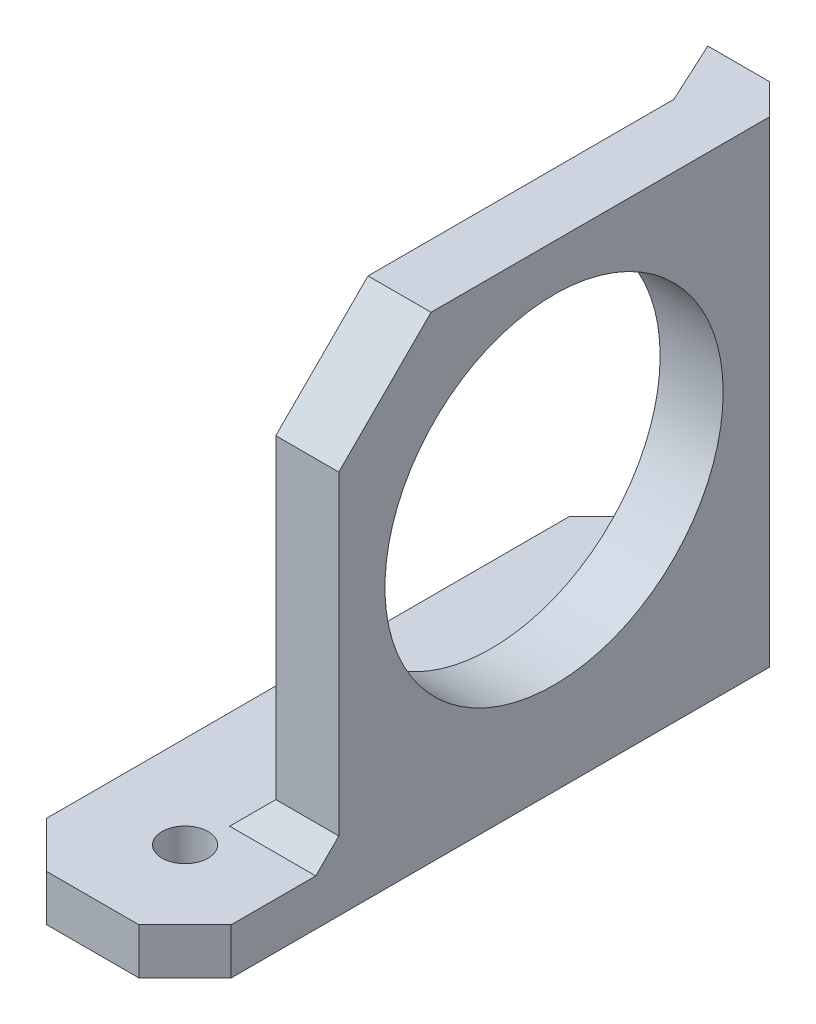
SolidWorks part; units mm, degrees
ref_plane "Front Plane" through (0, 0, 0) normal (0, 0, 1) x (1, 0, 0)
ref_plane "Top Plane" through (0, 0, 0) normal (0, 1, 0) x (1, 0, 0)
ref_plane "Right Plane" through (0, 0, 0) normal (1, 0, 0) x (0, 0, -1)
sketch "Sketch1" plane through (0, 0, 0) normal (0, 1, 0) x (1, 0, 0)
  line L0 (-6, 17) -> (-3, 20)
  line L1 (-3, 20) -> (6, 20)
  line L2 (-6, 17) -> (-6, -17)
  line L3 (-3, -20) -> (3, -20)
  line L4 (6, 20) -> (6, -17)
  line L5 (-6, 20) -> (6, -20) construction
  line L6 (-6, -20) -> (6, 20) construction
  line L8 (3, -20) -> (6, -17)
  line L9 (-6, -17) -> (-3, -20)
  circle A0 centre (0, 14) radius 1.5
  circle A1 centre (0, -14) radius 1.5
  point P0 (0, 0)
  dimension "D3" = 3
  dimension "D1" = 40
  dimension "D2" = 12
  dimension "D4" = 14
  dimension "D5" = 14
extrude "Boss-Extrude1" add sketch "Sketch1" along normal blind 3
sketch "Sketch2" plane through (0, 3, 0) normal (0, 1, 0) x (1, 0, 0)
  line L1 (6, -17) -> (6, 20) construction
  line L6 (6, -10) -> (6, 20)
  line L7 (6, 20) -> (0, 20)
  line L11 (1.9, -10) -> (1.9, 15.9)
  line L14 (6, 20) -> (-3, 20) construction
  line L16 (6, -10) -> (1.9, -10)
  line L17 (0, 20) -> (1.9, 15.9)
  line L18 (1.9, 15.9) -> (0, 15.9) construction
  dimension "D2" = 30
  dimension "D3" = 6
  dimension "3" = 4.1
extrude "Boss-Extrude2" add sketch "Sketch2" along normal blind 28 contours L16 L11 L17 L7 L6
chamfer "Chamfer1" distance 2 1 edges at (6, 15.5, -20)
sketch "Sketch4" plane through (6, 0, 0) normal (1, 0, 0) x (0, 0, -1)
  line L0 (-10, 31) -> (18, 31) construction
  line L1 (-17, 3) -> (-10, 3) construction
  circle A0 centre (4, 17) radius 11
  point P4 (4, 31)
  dimension "D1" = 22
  dimension "D2" = 14
extrude "Cut-Extrude1" cut sketch "Sketch4" against normal blind 11
chamfer "Chamfer2" distance 6 1 edges at (3.95, 31, 10)
chamfer "Chamfer3" distance 1.5 2 edges at (3.95, 3, 10) (1.9, 3, -2.95)
